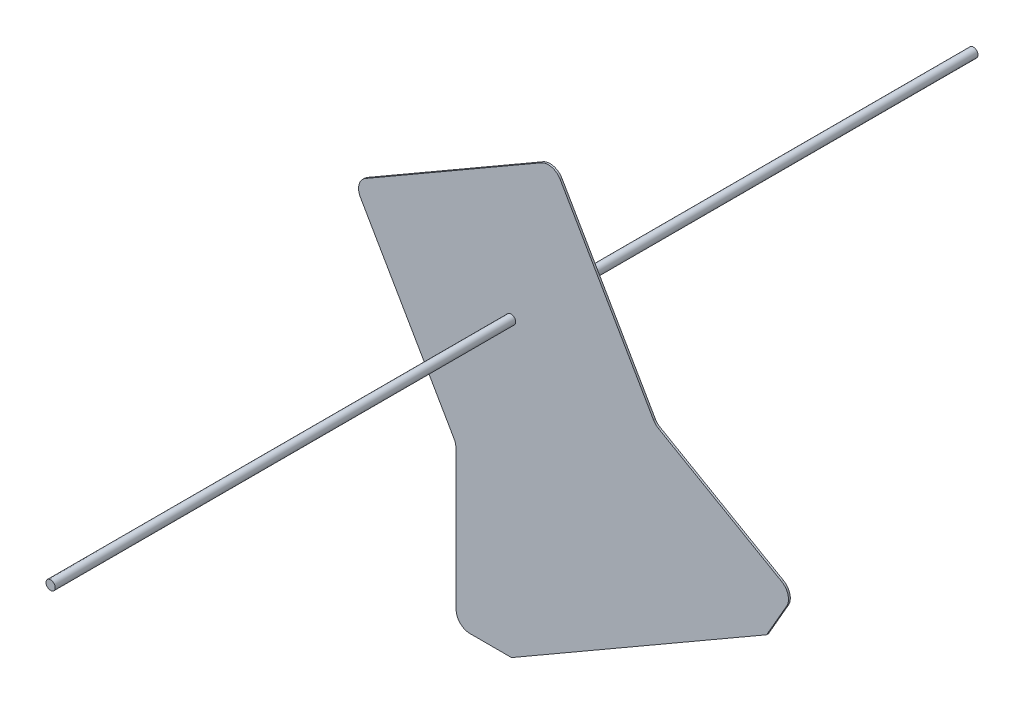
SolidWorks part; units mm, degrees
ref_plane "Front Plane" through (0, 0, 0) normal (0, 0, 1) x (1, 0, 0)
ref_plane "Top Plane" through (0, 0, 0) normal (0, 1, 0) x (1, 0, 0)
ref_plane "Right Plane" through (0, 0, 0) normal (1, 0, 0) x (0, 0, -1)
sketch "Sketch1" plane through (0, 0, 0) normal (0, 0, 1) x (1, 0, 0)
  line L0 (1528.9664, 0) -> (0, 0) construction
  line L1 (0, 0) -> (-918.1607, 1590.301) construction
  line L2 (0, 0) -> (-694.8278, -1203.4771) construction
  line L3 (0, 0) -> (-1542.2771, 0) construction
  line L4 (0, 0) -> (625.4451, 1083.3028) construction
  line L5 (0, 0) -> (646.494, -1119.7604) construction
  line L6 (-1000, 0) -> (-502.6514, 864.4892) construction
  line L7 (-502.6514, 864.4892) -> (502.6514, 864.4892) construction
  line L8 (502.6514, 864.4892) -> (1000, 0)
  line L9 (1000, 0) -> (500, -866.0254)
  line L10 (500, -866.0254) -> (-500, -866.0254)
  line L11 (-500, -866.0254) -> (-1000, 0)
  line L12 (1224.9953, 228.0643) -> (1224.9953, -221.9357)
  line L13 (-810.0072, 946.8449) -> (-420.2957, 1171.8449) construction
  line L14 (-810.0072, 946.8449) -> (-585.0072, 557.1335) construction
  line L15 (-585.0072, 557.1335) -> (-195.2957, 782.1335) construction
  line L16 (-420.2957, 1171.8449) -> (-195.2957, 782.1335) construction
  line L17 (-810.0072, 946.8449) -> (-195.2957, 782.1335) construction
  line L18 (-585.0072, 557.1335) -> (-420.2957, 1171.8449) construction
  line L19 (-500, -866.0254) -> (-502.6514, 864.4892) construction
  line L20 (-502.6514, 864.4892) -> (1000, 0)
  line L21 (1000, 0) -> (-500, -866.0254)
  line L22 (-599.9999, -866.1786) -> (-602.6513, 864.336) construction
  line L23 (-946.6097, 983.4474) -> (-58.6932, 745.5309) construction
  line L24 (-452.7842, 951.1682) -> (1049.8673, 86.679) construction
  line L25 (1050, -86.6025) -> (-450, -952.6279)
  line L26 (-602.6513, 864.336) -> (-502.6514, 864.4892) construction
  line L27 (1224.9953, -221.9357) -> (774.9953, -221.9357)
  line L28 (774.9953, 228.0643) -> (774.9953, -221.9357)
  line L29 (-452.7842, 951.1682) -> (-502.6514, 864.4892)
  line L30 (1224.9953, 228.0643) -> (774.9953, 228.0643)
  line L31 (1049.8673, 86.679) -> (1000, 0)
  line L32 (-414.9882, -1174.9092) -> (-804.6996, -949.9092)
  line L33 (1000, 0) -> (1050, -86.6025)
  line L34 (-450, -952.6279) -> (-500, -866.0254)
  line L35 (-804.6996, -949.9092) -> (-579.6996, -560.1978)
  line L36 (-189.9882, -785.1978) -> (-579.6996, -560.1978)
  line L37 (-599.9999, -866.1786) -> (-500, -866.0254)
  line L38 (-414.9882, -1174.9092) -> (-189.9882, -785.1978)
  line L39 (-594.1578, 522.9828) -> (-161.1451, 772.9828)
  line L40 (-844.1578, 955.9955) -> (-594.1578, 522.9828)
  line L41 (-844.1578, 955.9955) -> (-411.1451, 1205.9955)
  line L42 (-411.1451, 1205.9955) -> (-161.1451, 772.9828)
  line L43 (-594.1578, 522.9828) -> (-161.1451, 772.9828)
  line L44 (-844.1578, 955.9955) -> (-161.1451, 772.9828) construction
  line L45 (-411.1451, 1205.9955) -> (-594.1578, 522.9828) construction
  line L46 (-594.1578, 522.9828) -> (-444.1578, 263.1752)
  line L47 (-161.1451, 772.9828) -> (-11.1451, 513.1752)
  line L48 (-601.591, 172.2811) -> (148.4111, 605.295)
  line L49 (-601.591, 172.2811) -> (-602.1495, 536.8249)
  line L50 (148.4111, 605.295) -> (-170.1382, 788.5594)
  line L51 (49.7156, 546.7073) -> (109.5563, 650.7222)
  line L52 (-501.6792, 229.9652) -> (-621.6794, 229.9652)
  line L53 (-621.591, 172.2505) -> (-622.2028, 571.5581)
  line L54 (158.3846, 622.6308) -> (-190.0853, 823.1088)
  line L55 (-621.591, 172.2505) -> (-622.1495, 536.7943) construction
  line L56 (158.3846, 622.6308) -> (-160.1648, 805.8952) construction
  circle A0 centre (0, 0) radius 750 construction
  circle A1 centre (0, 0) radius 1000 construction
  circle A2 centre (-502.6514, 864.4892) radius 10
  point P31 (0, 0)
  point P32 (-18.2945, 0.0494)
  point P45 (0, 0)
  dimension "D1" = 1500
  dimension "D2" = 2000
  dimension "D5" = 20
  dimension "D3" = 120
  dimension "D4" = 1005.3029
  dimension "D6" = 60
  dimension "D7" = 60
  dimension "D8" = 450
  dimension "D9" = 100
  dimension "D11" = 60
  dimension "D12" = 500
  dimension "D10" = 500
  dimension "D14" = 300
  dimension "D15" = 20
  dimension "D16" = 20
  dimension "D13" = 3
extrude "Boss-Extrude1" add sketch "Sketch1" along normal mid plane 4 contours L46 L48 L47 L20 L39 | L42 L41 L40 L39 | L48 L50 L42 L47 L20 | L47 L39 L20 | L47 L48 L20 | L49 L48 L46 L40 | L29 A2 L20 | L20 A2 L29 | L53 L52 L49 L40 | L51 L54 L42 L50 region at (-11.0751, 558.8322, 0) region at (-24.4128, 654.4233, 0) region at (-312.257, 505.5123, 0) region at (-161.2522, 703.0675, 0) region at (-37.8148, 724.1714, 0) region at (-504.5832, 863.9684, 0) region at (-496.8562, 866.0515, 0) region at (-428.0129, 630.0602, 0) region at (-547.1765, 336.7479, 0) region at (-612.1065, 392.2334, 0)
extrude "Boss-Extrude2" add sketch "Sketch1<4>" along normal mid plane 2000 contours L29 A2 L20 | L20 A2 L29 region at (-504.5832, 863.9684, 0) region at (-496.8562, 866.0515, 0)
sketch "Sketch1<4>" plane through (0, 0, 0) normal (0, 0, 1) x (1, 0, 0) same geometry as "Sketch1"
fillet "Fillet1" radius 30 6 edges at (-190.0853, 823.1088, 0) (-622.2028, 571.5581, 0) (-621.6794, 229.9652, 0) (109.5563, 650.7222, 0) (-411.1451, 1205.9955, 0) (-844.1578, 955.9955, 0)
